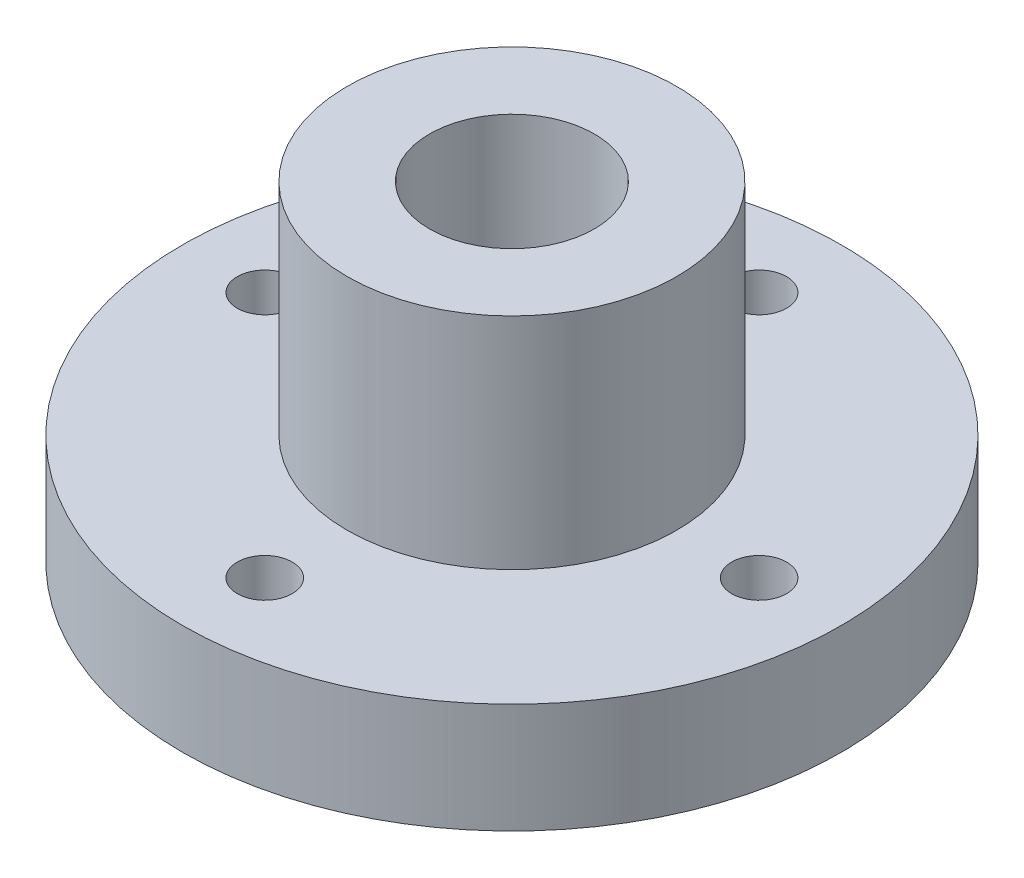
SolidWorks part; units mm, degrees
ref_plane "Front Plane" through (0, 0, 0) normal (0, 0, 1) x (1, 0, 0)
ref_plane "Top Plane" through (0, 0, 0) normal (0, 1, 0) x (1, 0, 0)
ref_plane "Right Plane" through (0, 0, 0) normal (1, 0, 0) x (0, 0, -1)
sketch "Sketch1" plane through (0, 0, 0) normal (0, 1, 0) x (1, 0, 0)
  circle A0 centre (0, 0) radius 3
  circle A1 centre (0, 0) radius 2.25 construction
  circle A2 centre (0, 0) radius 1.5
  circle A3 centre (0, 0) radius 0.75
  circle A4 centre (0, 2.25) radius 0.25
  circle A5 centre (2.25, 0) radius 0.25
  circle A6 centre (0, -2.25) radius 0.25
  circle A7 centre (-2.25, 0) radius 0.25
  point P8 (0, 0)
  point P9 (0, 0)
  dimension "D1" = 6
  dimension "D2" = 4.5
  dimension "D3" = 3
  dimension "D4" = 1.5
  dimension "D5" = 0.5
  dimension "D6" = 4
extrude "Boss-Extrude1" add sketch "Sketch1" along normal blind 1 contours A0 A7 A6 A5 A4 A2 region at (-2.9151, 0, 0)
extrude "Boss-Extrude2" add sketch "Sketch1<3>" along normal blind 3 contours A2 A3 region at (-1.4576, 0, 0)
sketch "Sketch1<3>" plane through (0, 0, 0) normal (0, 1, 0) x (1, 0, 0) same geometry as "Sketch1"
